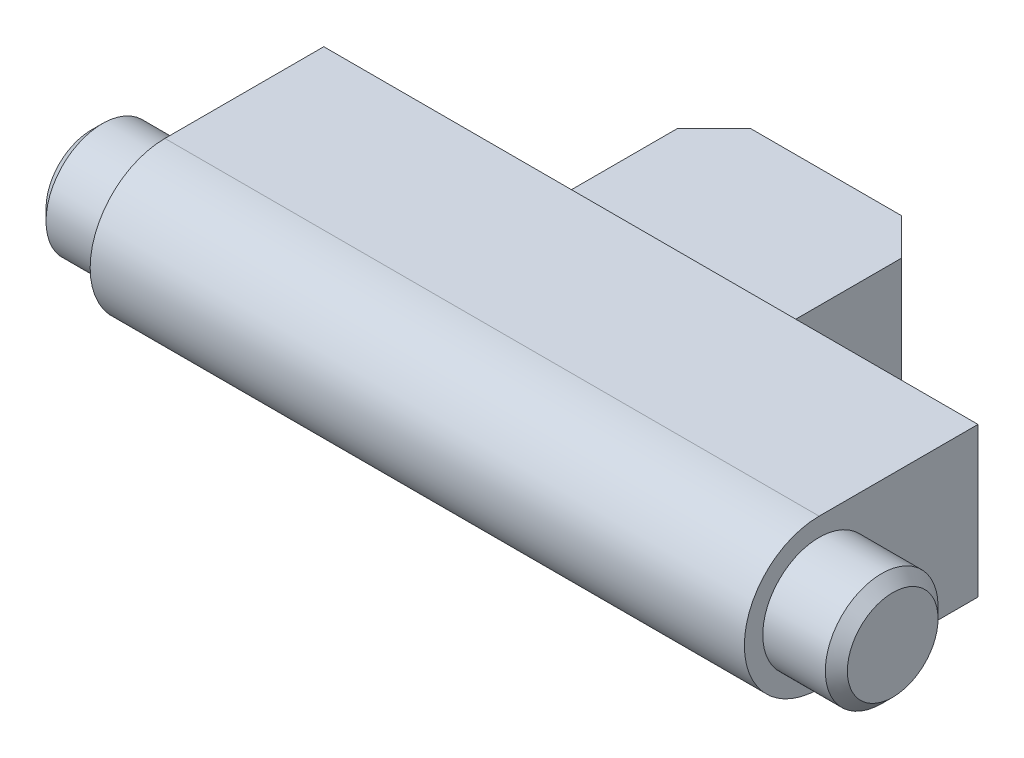
SolidWorks part; units mm, degrees
material "PET"
ref_plane "Front Plane" through (0, 0, 0) normal (0, 0, 1) x (1, 0, 0)
ref_plane "Top Plane" through (0, 0, 0) normal (0, 1, 0) x (1, 0, 0)
ref_plane "Right Plane" through (0, 0, 0) normal (1, 0, 0) x (0, 0, -1)
sketch "Sketch1" plane through (0, 0, 0) normal (0, 0, 1) x (1, 0, 0)
  line L0 (-3503.9715, 498.3353) -> (-3503.9715, 502.3993) construction
  line L6 (-3507.1465, 498.3353) -> (-3500.7965, 498.3353) construction
  line L9 (-3512.8615, 498.3353) -> (-3495.0815, 498.3353)
  line L10 (-3512.8615, 498.3353) -> (-3512.8615, 502.3993)
  line L11 (-3512.8615, 502.3993) -> (-3495.0815, 502.3993)
  line L12 (-3495.0815, 498.3353) -> (-3495.0815, 502.3993)
  line L13 (-3512.8615, 498.3353) -> (-3495.0815, 502.3993) construction
  line L14 (-3512.8615, 502.3993) -> (-3495.0815, 498.3353) construction
  point P8 (-3503.9715, 500.3673)
  dimension "D1" = 17.78
  dimension "D2" = 4.064
extrude "Boss-Extrude1" add sketch "Sketch1" along normal blind 6.35
fillet "Fillet1" 2 edges at (-3503.9715, 502.3993, 6.35) (-3503.9715, 498.3353, 6.35) type full round first side face at (-3503.9715, 502.3993, 3.175) second side face at (-3503.9715, 498.3353, 3.175) middle face at (-3503.9715, 500.3673, 6.35)
sketch "Sketch2" plane through (-3512.8615, 0, 0) normal (-1, 0, 0) x (0, 0, 1)
  arc A2 (4.318, 498.8353) -> (4.318, 501.8993) centre (4.318, 500.3673) ccw
  circle A3 centre (4.318, 500.3673) radius 1.532
  dimension "D1" = 0.5
extrude "Boss-Extrude2" add sketch "Sketch2" along normal blind 2
chamfer "Chamfer1" distance 0.3 angle 45 1 edges at (-3514.8615, 498.8353, 4.318)
ref_plane "Plane4" through (-3503.9715, 0, 0) normal (-1, 0, 0) x (0, 0, 1)
mirror "Mirror1" about plane through (-3503.9715, 0, 0) normal (-1, 0, 0) of "Chamfer1", "Boss-Extrude2"
sketch "Sketch3" plane through (0, 0, 0) normal (0, 0, -1) x (-1, 0, 0)
  line L8 (3500.9235, 498.4623) -> (3507.0195, 498.4623)
  line L9 (3500.9235, 501.5103) -> (3500.9235, 498.4623)
  line L10 (3507.0195, 501.5103) -> (3500.9235, 501.5103)
  line L11 (3507.0195, 498.4623) -> (3507.0195, 501.5103)
  line L12 (3500.9235, 498.4623) -> (3507.0195, 498.4623)
  line L13 (3500.9235, 501.5103) -> (3500.9235, 498.4623)
  line L14 (3507.0195, 501.5103) -> (3500.9235, 501.5103)
  line L15 (3507.0195, 498.4623) -> (3507.0195, 501.5103)
  dimension "D1" = 0.127
extrude "Boss-Extrude3" add sketch "Sketch3" along normal blind 4.7625
sketch "Sketch4" plane through (0, 498.4623, 0) normal (0, -1, 0) x (1, 0, 0)
  line L4 (-3500.9235, 0) -> (-3507.0195, 0)
  line L5 (-3507.0195, 0) -> (-3507.0195, -4.7625)
  line L6 (-3507.0195, -4.7625) -> (-3500.9235, -4.7625)
  line L7 (-3500.9235, -4.7625) -> (-3500.9235, 0)
  line L8 (-3500.9235, 0) -> (-3507.0195, 0)
  line L9 (-3507.0195, 0) -> (-3507.0195, -4.7625)
  line L10 (-3507.0195, -4.7625) -> (-3500.9235, -4.7625)
  line L11 (-3500.9235, -4.7625) -> (-3500.9235, 0)
  dimension "D1" = 0
extrude "Boss-Extrude4" add sketch "Sketch4" along normal up to surface (0.127 mm away) up to face at (-3503.9715, 498.3353, 2.159)
chamfer "Chamfer2" distance 1 angle 45 2 edges at (-3507.0195, 499.9228, -4.7625) (-3500.9235, 499.9228, -4.7625)
